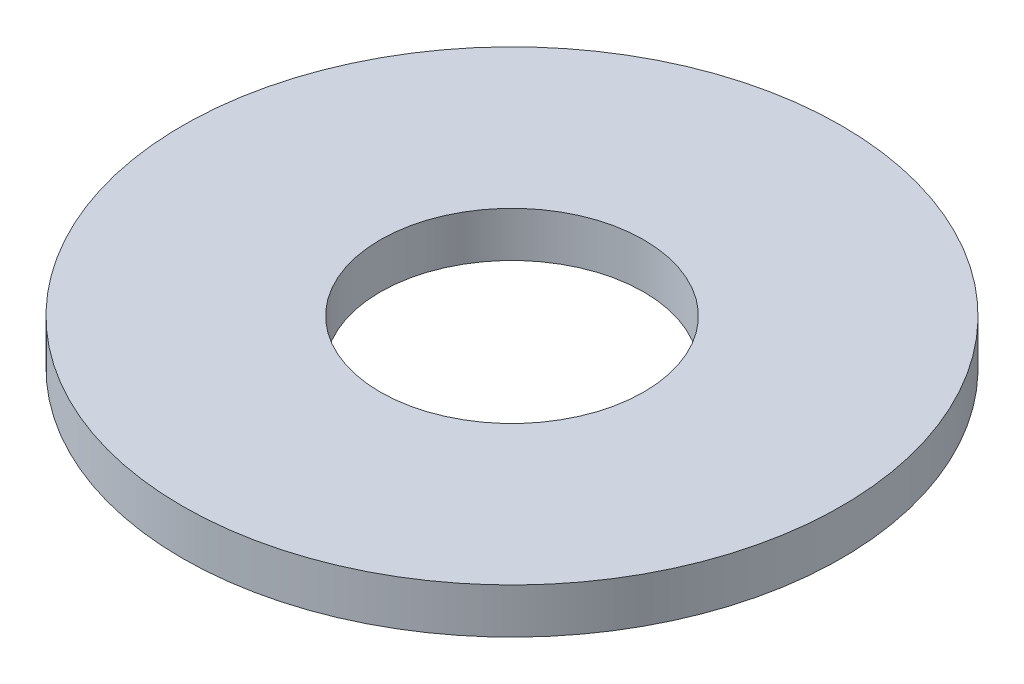
SolidWorks part; units mm, degrees
ref_plane "Front Plane" through (0, 0, 0) normal (0, 0, 1) x (1, 0, 0)
ref_plane "Top Plane" through (0, 0, 0) normal (0, 1, 0) x (1, 0, 0)
ref_plane "Right Plane" through (0, 0, 0) normal (1, 0, 0) x (0, 0, -1)
sketch "Sketch1" plane through (0, 0, 0) normal (0, 1, 0) x (1, 0, 0)
  circle A0 centre (0, 0) radius 87.5
  dimension "FLANGE_OD" = 175
extrude "Boss-Extrude1" add sketch "Sketch1" along normal blind 12
sketch "Sketch2" plane through (0, 0, 0) normal (0, 1, 0) x (1, 0, 0)
  circle A0 centre (0, 0) radius 35
  dimension "BORE_D" = 70
extrude "Cut-Extrude1" cut sketch "Sketch2" along normal through all
sketch "Sketch3" plane through (0, 12, 0) normal (0, 1, 0) x (1, 0, 0)
  circle A0 centre (0, 0) radius 21.4949 construction
  circle A1 centre (-21.4949, 0) radius 6.9064
  dimension "BOLT_D" = 13.8128
  dimension "BOLT_PCD" = 42.9899
extrude "Cut-Extrude2" cut sketch "Sketch3" against normal blind 10.1375 rebuild error yes
pattern_circular "CirPattern1" count 4 over 360 rebuild error yes
